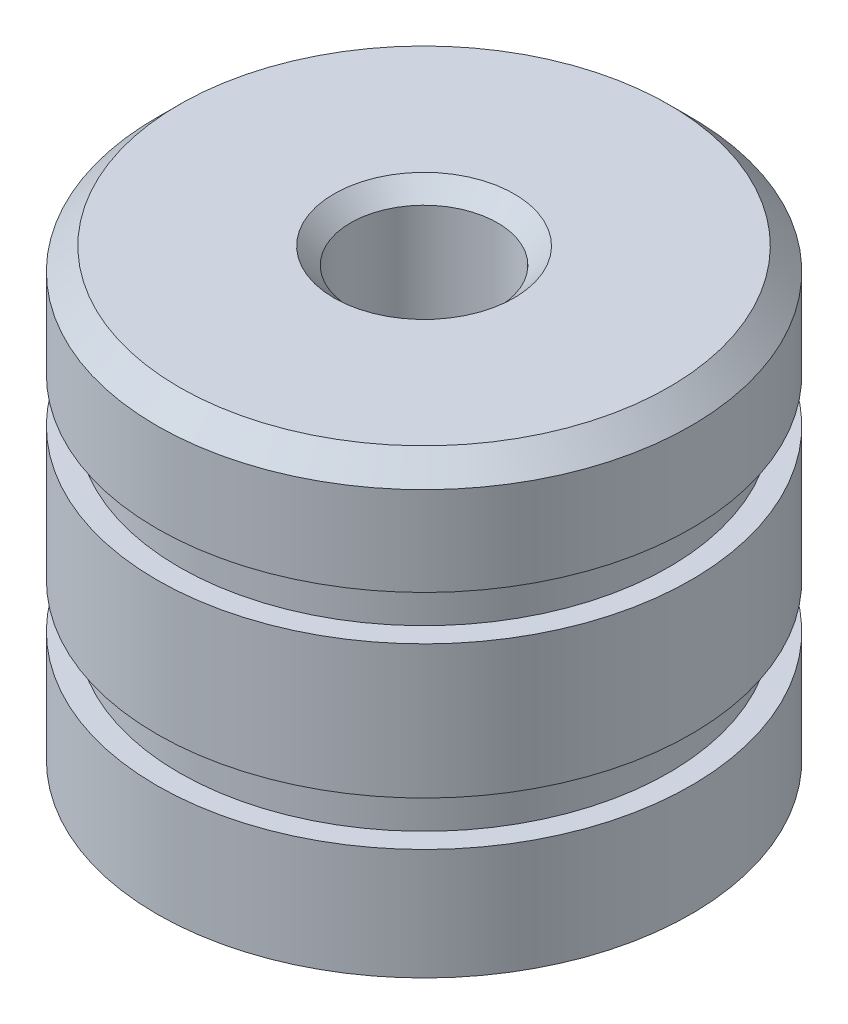
SolidWorks part; units mm, degrees
ref_plane "Front Plane" through (0, 0, 0) normal (0, 0, 1) x (1, 0, 0)
ref_plane "Top Plane" through (0, 0, 0) normal (0, 1, 0) x (1, 0, 0)
ref_plane "Right Plane" through (0, 0, 0) normal (1, 0, 0) x (0, 0, -1)
sketch "Sketch1" plane through (0, 0, 0) normal (0, 1, 0) x (1, 0, 0)
  circle A0 centre (0, 0) radius 6
  dimension "D1" = 12
extrude "Boss-Extrude1" add sketch "Sketch1" along normal mid plane 10
sketch "Sketch2" plane through (0, 5, 0) normal (0, 1, 0) x (1, 0, 0)
  circle A0 centre (0, 0) radius 5.5
  circle A2 centre (0, 0) radius 6
  circle A3 centre (0, 0) radius 6
  dimension "D1" = 11
  dimension "D2" = 0
extrude "Cut-Extrude1" cut sketch "Sketch2" against normal blind 1 from offset 2.5 offset against normal yes
mirror "Mirror1" about plane through (0, 0, 0) normal (0, 1, 0) of "Cut-Extrude1"
chamfer "Chamfer1" distance 0.5 angle 45 1 edges at (0, 5, 6)
hole_wizard "M4x0.7 Tapped Hole1" positions "Sketch3" profile "Sketch4" tap size "M4x0.7" standard "ANSI Metric"
sketch "Sketch3" plane through (0, 5, 0) normal (0, 1, 0) x (1, 0, 0)
  point P0 (0, 0)
sketch "Sketch4" plane through (0, 5, 0) normal (1, 0, 0) x (0, 0, 1)
  line L0 (0, 0) -> (0, 8.9914)
  line L1 (0, 8.9914) -> (1.65, 8)
  line L2 (1.65, 8) -> (1.65, 0.375)
  line L3 (1.65, 0.375) -> (2.025, 0)
  line L5 (2.025, 0) -> (0, 0)
  line L6 (-1.65, 0.375) -> (-2.025, 0) construction
  line L10 (0, 8.9914) -> (-1.65, 8) construction
  line L11 (0, -6.35) -> (0, 107.95) construction
  dimension "Tap Drill Dia." = 3.3
  dimension "Tap Drill Depth" = 8
  dimension "Near C'Sink Dia." = 4.05
  dimension "Near C'Sink Angle" = 90
  dimension "Drill Angle" = 118
cosmetic thread "Hole Thread1" parameters "D1"=8, "D2"=4
